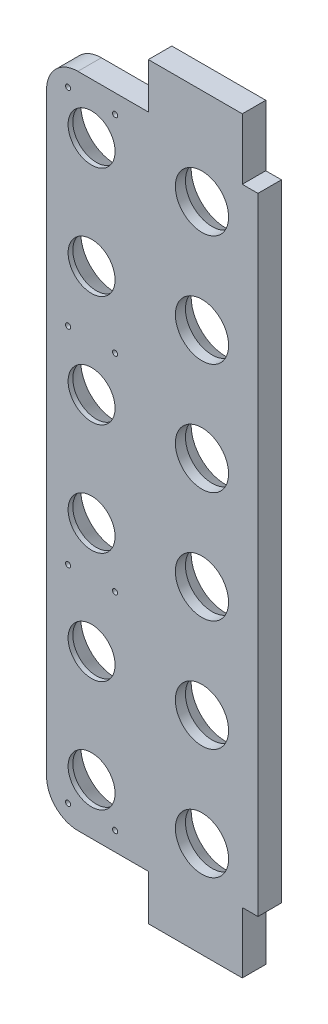
SolidWorks part; units mm, degrees
ref_plane "Front" through (0, 0, 0) normal (0, 0, 1) x (1, 0, 0)
ref_plane "Top" through (0, 0, 0) normal (0, 1, 0) x (1, 0, 0)
ref_plane "Right" through (0, 0, 0) normal (1, 0, 0) x (0, 0, -1)
sketch "Esquisse1" plane through (0, 0, 0) normal (0, 0, 1) x (1, 0, 0)
  line L1 (0, 0) -> (125, 0)
  line L2 (0, 0) -> (0, 420)
  line L3 (0, 420) -> (125, 420)
  line L4 (125, 0) -> (125, 420)
  dimension "D1" = 420
  dimension "D2" = 125
extrude "Boss.-Extru.1" add sketch "Esquisse1" along normal blind 15
sketch "Esquisse2" plane through (0, 0, 15) normal (0, 0, 1) x (1, 0, 0)
  line L0 (64, 0) -> (64, 420) construction
  line L1 (0, 0) -> (125, 0) construction
  line L2 (125, 420) -> (0, 420) construction
  line L3 (64, 210) -> (0, 210) construction
  line L4 (0, 420) -> (0, 0) construction
  line L5 (28.75, 210) -> (28.75, 245.5) construction
  line L6 (64, 139) -> (0, 139) construction
  line L7 (64, 68) -> (0, 68) construction
  line L8 (64, 352) -> (0, 352) construction
  circle A0 centre (28.75, 245.5) radius 15
  circle A1 centre (99.25, 245.5) radius 15
  circle A2 centre (99.25, 174.5) radius 15
  circle A3 centre (28.75, 174.5) radius 15
  circle A4 centre (28.75, 103.5) radius 15
  circle A5 centre (99.25, 103.5) radius 15
  circle A6 centre (99.25, 32.5) radius 15
  circle A7 centre (28.75, 32.5) radius 15
  circle A8 centre (28.75, 387.5) radius 15
  circle A9 centre (99.25, 387.5) radius 15
  circle A10 centre (99.25, 316.5) radius 15
  circle A11 centre (28.75, 316.5) radius 15
  dimension "D1" = 30
  dimension "D2" = 71
  dimension "D3" = 70.5
  dimension "D5" = 71
  dimension "D6" = 71
  dimension "D4" = 64
extrude "Enlèv. mat.-Extru.1" cut sketch "Esquisse2" against normal through all both and the other way through all
chamfer "Chanfrein1" distance 12 angle 30 12 edges at (13.75, 32.5, 0) (43.75, 103.5, 0) (13.75, 174.5, 0) (43.75, 245.5, 0) (13.75, 316.5, 0) (43.75, 387.5, 0) (114.25, 32.5, 0) (84.25, 103.5, 0) (114.25, 174.5, 0) (84.25, 245.5, 0) (114.25, 316.5, 0) (84.25, 387.5, 0) first distance on face at (13.75, 32.5, 0) first distance on face at (43.75, 103.5, 0) first distance on face at (13.75, 174.5, 0) first distance on face at (43.75, 245.5, 0) first distance on face at (13.75, 316.5, 0) first distance on face at (43.75, 387.5, 0) first distance on face at (114.25, 32.5, 0) first distance on face at (84.25, 103.5, 0) first distance on face at (114.25, 174.5, 0) first distance on face at (84.25, 245.5, 0) first distance on face at (114.25, 316.5, 0) first distance on face at (84.25, 387.5, 0)
sketch "Esquisse3" plane through (0, 0, 15) normal (0, 0, 1) x (1, 0, 0)
  line L0 (125, 210) -> (0, 210) construction
  line L1 (125, 420) -> (65, 420)
  line L2 (125, 420) -> (125, 449)
  line L3 (125, 449) -> (65, 449)
  line L4 (65, 420) -> (65, 449)
  line L5 (125, 0) -> (125, 420) construction
  line L6 (0, 420) -> (0, 0) construction
  line L7 (65, 0) -> (65, -29)
  line L8 (125, -29) -> (65, -29)
  line L9 (125, 0) -> (125, -29)
  line L10 (125, 0) -> (65, 0)
  dimension "D1" = 60
  dimension "D2" = 478
extrude "Boss.-Extru.2" add sketch "Esquisse3" against normal up to vertex (15 mm away) up to point (125, 420, 0)
fillet "Congé1" radius 20 2 edges at (0, 420, 7.5) (0, 0, 7.5)
sketch "Esquisse4" plane through (0, 0, 15) normal (0, 0, 1) x (1, 0, 0)
  line L0 (28.75, 32.5) -> (28.75, 387.5) construction
  line L1 (28.75, 210) -> (0, 210) construction
  line L2 (0, 400) -> (0, 20) construction
  line L3 (13.75, 210) -> (13.75, 408) construction
  circle A0 centre (13.75, 408) radius 1.65
  circle A1 centre (13.75, 276) radius 1.65
  circle A2 centre (43.75, 276) radius 1.65
  circle A3 centre (43.75, 408) radius 1.65
  circle A4 centre (43.75, 12) radius 1.65
  circle A5 centre (43.75, 144) radius 1.65
  circle A6 centre (13.75, 144) radius 1.65
  circle A7 centre (13.75, 12) radius 1.65
  dimension "D1" = 132
  dimension "D2" = 132
  dimension "D3" = 3.3
  dimension "D4" = 15
extrude "Enlèv. mat.-Extru.2" cut sketch "Esquisse4" against normal through all both and the other way through all
sketch "Esquisse5" plane through (0, 0, 15) normal (0, 0, 1) x (1, 0, 0)
  line L0 (125, -29) -> (125, 449) construction
  line L1 (125, 10) -> (135, 10)
  line L2 (125, 10) -> (125, 410)
  line L3 (125, 410) -> (135, 410)
  line L4 (135, 10) -> (135, 410)
  line L5 (135, 210) -> (0, 210) construction
  line L6 (0, 400) -> (0, 20) construction
  dimension "D1" = 10
  dimension "D2" = 400
extrude "Boss.-Extru.3" add sketch "Esquisse5" against normal up to vertex (15 mm away) up to point (125, -29, 0)
sketch "Esquisse6" plane through (0, 0, 15) normal (0, 0, 1) x (1, 0, 0)
  circle A0 centre (99.25, 32.5) radius 17
  circle A1 centre (99.25, 103.5) radius 17
  circle A2 centre (99.25, 174.5) radius 17
  circle A3 centre (99.25, 245.5) radius 17
  circle A4 centre (99.25, 316.5) radius 17
  circle A5 centre (99.25, 387.5) radius 17
  dimension "D1" = 34
extrude "Enlèv. mat.-Extru.3" cut sketch "Esquisse6" against normal through all both and the other way through all
